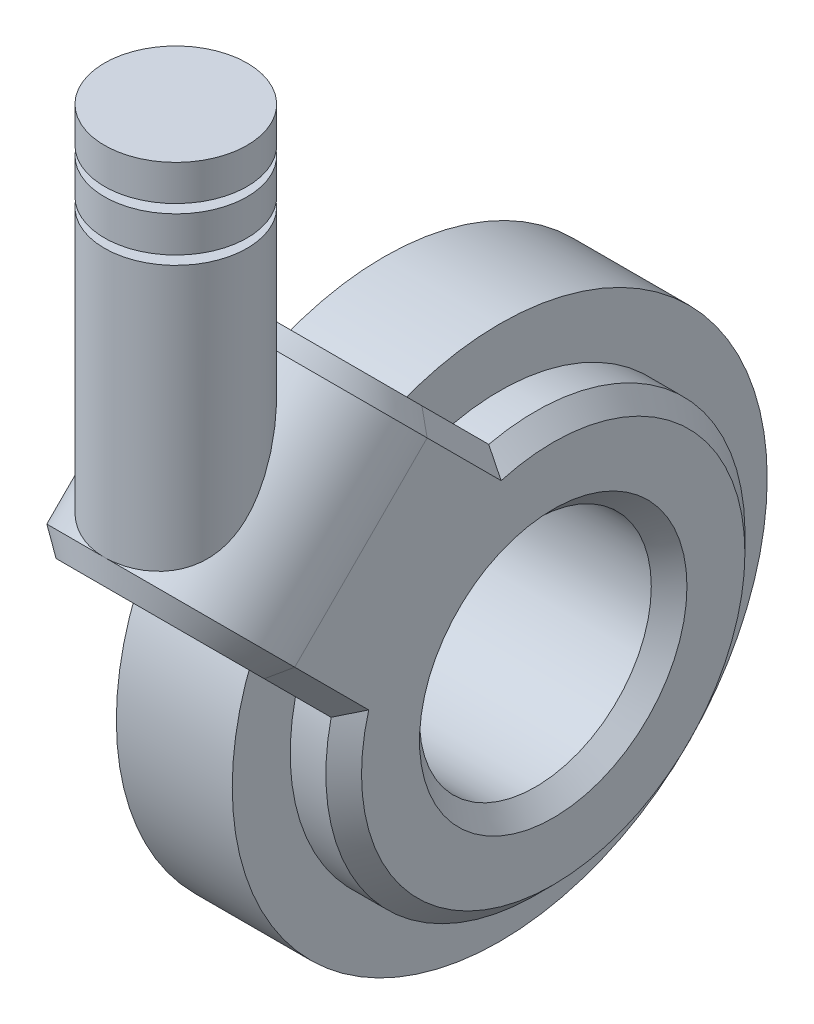
SolidWorks part; units mm, degrees
ref_plane "Front Plane" through (0, 0, 0) normal (0, 0, 1) x (1, 0, 0)
ref_plane "Top Plane" through (0, 0, 0) normal (0, 1, 0) x (1, 0, 0)
ref_plane "Right Plane" through (0, 0, 0) normal (1, 0, 0) x (0, 0, -1)
sketch "Sketch1" plane through (0, 0, 0) normal (1, 0, 0) x (0, 0, -1)
  circle A0 centre (0, 0) radius 13.5
  circle A1 centre (0, 0) radius 30
  dimension "D1" = 60
  dimension "D2" = 27
extrude "Boss-Extrude1" add sketch "Sketch1" along normal mid plane 13
sketch "Sketch2" plane through (0, 0, 0) normal (1, 0, 0) x (0, 0, -1)
  circle A0 centre (0, 0) radius 13
  circle A1 centre (0, 0) radius 23.5
  dimension "D1" = 47
  dimension "D2" = 26
extrude "Boss-Extrude2" add sketch "Sketch2" along normal mid plane 25 separate body
ref_plane "Plane1" through (0, 0, 0) normal (0, 0.7071, -0.7071) x (-1, 0, 0)
sketch "Sketch4" plane through (0, 0, 0) normal (0, 0.7071, -0.7071) x (-1, 0, 0)
  line L0 (-12.5, 18.5) -> (-12.5, 30.5)
  line L1 (12.5, 18.5) -> (12.5, 30.5)
  line L3 (-12.5, 18.5) -> (-7.5, 18.5)
  line L4 (-7.5, 18.5) -> (-7.5, 30.5)
  line L5 (12.5, 18.5) -> (7.5, 18.5)
  line L7 (7.5, 18.5) -> (7.5, 30.5)
  line L8 (6.5, 30) -> (-6.5, 30) construction
  line L10 (12.5, -23.5) -> (12.5, 23.5) construction
  line L11 (-12.5, 23.5) -> (-12.5, -23.5) construction
  line L12 (12.5, 23.5) -> (-12.5, 23.5) construction
  line L13 (12.5, 23.5) -> (-12.5, 23.5) construction
  arc A0 (12.5, 30.5) -> (-12.5, 30.5) centre (0, 30.5) ccw
  arc A1 (7.5, 30.5) -> (-7.5, 30.5) centre (0, 30.5) ccw
  point P2 (12.5, 23.5)
  point P6 (12.5, 23.5)
  point P7 (12.4256, 22.6477)
  point P13 (7.4286, 22.4398)
  point P16 (0, 38)
  point P17 (0, 43)
  point P18 (0, 0)
  point P19 (0, 0)
  point P22 (0, 0)
  point P23 (12.5, 23.9507)
  point P25 (0, 0)
  point P26 (-12.3842, 22.8213)
  point P27 (-12.5, 23.5)
  point P28 (0, 0)
  point P29 (7.4446, 23.5)
  dimension "D1" = 5
  dimension "D2" = 5
  dimension "D3" = 5
  dimension "D4" = 13
  dimension "D5" = 5
  dimension "D6" = 5
extrude "Boss-Extrude3" add sketch "Sketch4" along normal mid plane 25
chamfer "Chamfer1" distance 2 angle 45 10 edges at (-12.5, 0, -13) (-12.5, 26.6578, 8.9802) (-12.5, 8.9802, 26.6578) (-12.5, -16.617, -16.617) (12.5, 0, -13) (0, 21.5668, 39.2444) (0, 39.2444, 21.5668) (12.5, 8.9802, 26.6578) (12.5, 26.6578, 8.9802) (12.5, -16.617, -16.617)
ref_plane "Plane2" through (0, 53, 0) normal (0, 1, 0) x (1, 0, 0)
sketch "Sketch5" plane through (0, 53, 0) normal (0, 1, 0) x (1, 0, 0)
  line L0 (0, -55) -> (0, 55) construction
  circle A0 centre (0, -29.8302) radius 8
  ellipse E0 centre (0, -28.9914) end of major axis (12.5, -28.9914) minor radius 8.8388 (-12.5, -28.9914) -> (12.5, -28.9914) ccw construction
  ellipse E1 centre (0, -28.9914) end of major axis (12.5, -28.9914) minor radius 8.8388 (-12.5, -28.9914) -> (12.5, -28.9914) ccw construction
  point P15 (0, 0)
  dimension "D1" = 16
extrude "Boss-Extrude4" add sketch "Sketch5" against normal up to next contours A0
sketch "Sketch6" plane through (0, 0, 0) normal (1, 0, 0) x (0, 0, -1)
  line L0 (-29.8302, 53) -> (-29.8302, 63)
  line L1 (-21.8302, 53) -> (-37.8302, 53) construction
  line L2 (-29.8302, 63) -> (-21.8302, 63)
  line L3 (-21.8302, 63) -> (-21.8302, 59)
  line L4 (-21.8302, 59) -> (-23.8302, 59)
  line L5 (-23.8302, 59) -> (-23.8302, 58)
  line L6 (-23.8302, 58) -> (-21.8302, 58)
  line L7 (-21.8302, 58) -> (-21.8302, 54)
  line L8 (-21.8302, 54) -> (-23.8302, 54)
  line L9 (-23.8302, 54) -> (-23.8302, 53)
  line L10 (-23.8302, 53) -> (-29.8302, 53)
  dimension "D1" = 2
  dimension "D2" = 1
  dimension "D3" = 1
  dimension "D4" = 4
  dimension "D5" = 10
revolve "Revolve1" add sketch "Sketch6" angle 360 about L0
